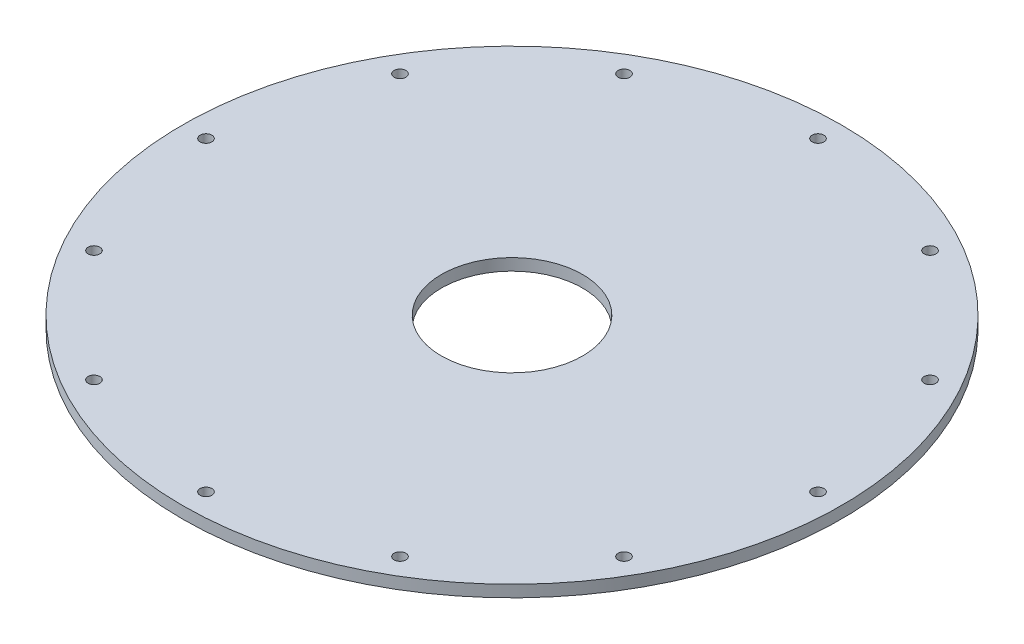
SolidWorks part; units mm, degrees
material "6063-T6"
ref_plane "Front Plane" through (0, 0, 0) normal (0, 0, 1) x (1, 0, 0)
ref_plane "Top Plane" through (0, 0, 0) normal (0, 1, 0) x (1, 0, 0)
ref_plane "Right Plane" through (0, 0, 0) normal (1, 0, 0) x (0, 0, -1)
ref_axis "Axis1" through (0, 55, 0) along (0, -1, 0)
sketch "Sketch1" plane through (0, 0, 0) normal (0, 0, 1) x (1, 0, 0)
  line L0 (-44.45, 0) -> (-9.525, 0)
  line L1 (0, 55) -> (0, -55) construction
  line L2 (-44.45, 0) -> (-44.45, 1.5875)
  line L3 (-44.45, 1.5875) -> (-9.525, 1.5875)
  line L4 (-44.45, 1.5875) -> (-9.525, 1.5875) construction
  line L5 (-9.525, 1.5875) -> (-9.525, 0)
  line L6 (-9.525, 0) -> (0, 0) construction
  line L7 (-44.45, 0) -> (-44.45, 1.5875) construction
  line L8 (-9.525, 1.5875) -> (-9.525, 0) construction
revolve "Revolve1" add sketch "Sketch1" angle 360 about axis through (0, 55, 0) along (0, -1, 0)
ref_plane "Hole Location Plane" through (0, 3.175, 0) normal (0, 1, 0) x (1, 0, 0)
sketch "Hole Location" plane through (0, 3.175, 0) normal (0, 1, 0) x (1, 0, 0)
  line L0 (0, 0) -> (-41.275, 0) construction
  circle A0 centre (0, 0) radius 41.275 construction
  dimension "D1" = 82.55
hole_wizard "1/16 (0.0625) Diameter Hole1" positions "Sketch4" profile "Sketch5" hole size "1/16" standard "ANSI Inch" end condition through all
sketch "Sketch4" plane through (0, 1.5875, 0) normal (0, 1, 0) x (1, 0, 0)
  point P0 (-41.275, 0)
sketch "Sketch5" plane through (-41.275, 1.5875, 0) normal (1, 0, 0) x (0, 0, 1)
  line L0 (0, 0) -> (0, 1.5875)
  line L1 (0, 1.5875) -> (0.7937, 1.5875)
  line L2 (0.7937, 1.5875) -> (0.7937, 0)
  line L5 (0.7937, 0) -> (0, 0)
  line L11 (0, -6.35) -> (0, 107.95) construction
  dimension "Thru Hole Dia." = 1.5875
  dimension "Thru Hole Depth" = 1.5875
pattern_circular "CirPattern1" count 12 every 30 about axis through (0, 55, 0) along (0, -1, 0) of "1/16 (0.0625) Diameter Hole1"
equation "\"D1@Hole Location\"=\"TANK DIAMETER@Cryo Tank.Assembly\"+\"GASKET SEAT THICKNESS@Cryo Tank.Assembly\""
